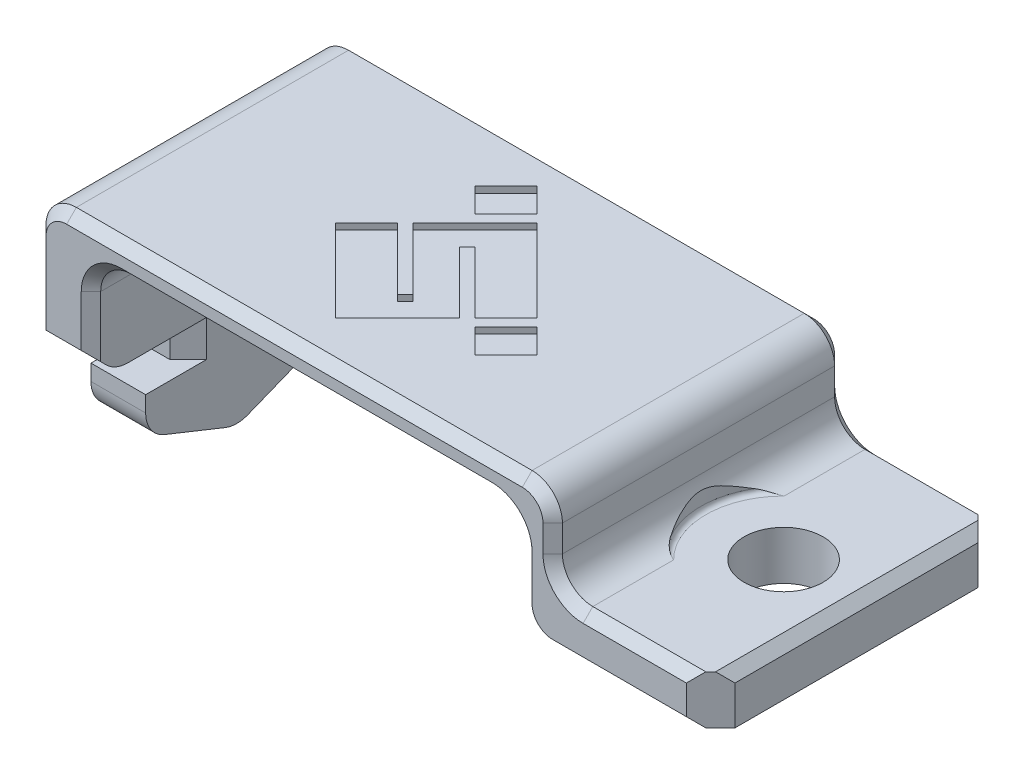
SolidWorks part; units mm, degrees
material "ABS_eSun_GRN"
ref_plane "Front Plane" through (0, 0, 0) normal (0, 0, 1) x (1, 0, 0)
ref_plane "Top Plane" through (0, 0, 0) normal (0, 1, 0) x (1, 0, 0)
ref_plane "Right Plane" through (0, 0, 0) normal (1, 0, 0) x (0, 0, -1)
ref_plane "shelf" through (0, -2.2, 0) normal (0, 1, 0) x (1, 0, 0)
sketch "Sketch1" plane through (0, 0, 0) normal (0, 0, 1) x (1, 0, 0)
  line L0 (-17.75, -9.5) -> (-17.75, 9.5)
  line L1 (-17.75, 9.5) -> (17.75, 9.5)
  line L2 (17.75, 9.5) -> (17.75, 0.8)
  line L5 (20.25, 12) -> (-22.25, 12)
  line L6 (-22.25, 12) -> (-22.25, -9.5)
  line L7 (-22.25, -9.5) -> (-17.75, -9.5)
  line L8 (-22.25, -2.2) -> (31.75, -2.2) construction
  line L9 (-17.75, 7.5) -> (17.75, 7.5) construction
  line L10 (20.25, 4.8) -> (20.25, 12)
  line L13 (20.25, 4.8) -> (33.25, 4.8)
  line L14 (33.25, 0.8) -> (33.25, 4.8)
  line L15 (17.75, 0.8) -> (33.25, 0.8)
  line L16 (-30.0367, 0) -> (47.996, 0) construction
  line L17 (55, -2.2) -> (-55, -2.2) construction
  point P2 (0, 9.5)
  dimension "D1" = 35.5
  dimension "D2" = 2.5
  dimension "D3" = 4.5
  dimension "D4" = 19
  dimension "D8" = 2
  dimension "D9" = 13
  dimension "D10" = 2.5
  dimension "D5" = 3
  dimension "D11" = 4
  dimension "D6" = 11.7
  dimension "D7" = 7.5
extrude "boss_body" add sketch "Sketch1" along normal mid plane 24
fillet "Fillet1" radius 2.5 5 edges at (17.75, 9.5, 0) (-17.75, 9.5, 0) (-22.25, 12, 0) (20.25, 12, 0) (20.25, 4.8, 0)
sketch "Sketch2" plane through (0, 0, 0) normal (1, 0, 0) x (0, 0, -1)
  line L0 (-7.5, -2.2) -> (-7.5, -5.2)
  line L1 (-12, 0.8) -> (-4, 0.8)
  line L2 (-12, 0.8) -> (-12, -9.5)
  line L4 (-4, 0.8) -> (-4, -2.2)
  line L5 (-7.5, -5.2) -> (0, -8.2)
  line L6 (12, 0.8) -> (4, 0.8)
  line L7 (12, 0.8) -> (12, -3.636)
  line L9 (4, 0.8) -> (4, -2.2)
  line L10 (55, -2.2) -> (-55, -2.2) construction
  line L11 (12, -9.5) -> (12, 7) construction
  line L12 (-12, -9.5) -> (-12, 7) construction
  line L13 (0, 12) -> (0, -9.5) construction
  line L14 (0, -8.2) -> (7.5, -5.2)
  line L15 (7.5, -5.2) -> (7.5, -2.2)
  line L16 (-7.5, -5.2) -> (7.5, -5.2) construction
  line L18 (-12, -9.5) -> (12, -9.5)
  line L19 (-12, -9.5) -> (12, -9.5) construction
  line L20 (12, -9.5) -> (12, -3.636)
  line L21 (-4, -2.2) -> (-7.5, -2.2)
  line L22 (7.5, -2.2) -> (4, -2.2)
  point P14 (0, -5.2)
  dimension "D1" = 8
  dimension "D2" = 3
  dimension "D3" = 15
  dimension "D4" = 6
  dimension "D5" = 3
extrude "cut-notch" cut sketch "Sketch2" against normal through all
sketch "Sketch3" plane through (17.75, 0, 0) normal (-1, 0, 0) x (0, 0, 1)
  line L0 (-5, 0.8) -> (-1, -3.2)
  line L2 (-1, -3.2) -> (1, -3.2)
  line L3 (1, -3.2) -> (5, 0.8)
  line L4 (5, 0.8) -> (-5, 0.8)
  line L5 (12, 0.8) -> (-12, 0.8) construction
  point P4 (0, 0.8)
  point P7 (0, -3.2)
  dimension "D1" = 45
  dimension "D2" = 4
  dimension "D3" = 10
extrude "boss_finger" add sketch "Sketch3" against normal blind 2.5
sketch "Sketch4" plane through (0, 0, 0) normal (0, 0, 1) x (1, 0, 0)
  line L0 (-3, 9.5) -> (-1, 7.5)
  line L1 (-17.75, 9.5) -> (17.75, 9.5) construction
  line L2 (-1, 7.5) -> (1, 7.5)
  line L3 (1, 7.5) -> (3, 9.5)
  line L4 (3, 9.5) -> (-3, 9.5)
  line L6 (-15.25, 9.5) -> (15.25, 9.5) construction
  point P4 (0, 7.5)
  point P7 (0, 9.5)
  dimension "D1" = 2
  dimension "D2" = 2
extrude "boss_press" add sketch "Sketch4" along normal mid plane 24 separate body
chamfer "Chamfer3" distance 3 angle 45 2 edges at (0, 7.5, -12) (0, 7.5, 12)
sketch "Sketch6" plane through (0, 0, 0) normal (0, 1, 0) x (1, 0, 0)
  line L0 (20.25, -12) -> (20.25, 12) construction
  circle A0 centre (27.25, 0) radius 3.25
  dimension "D1" = 6.5
  dimension "D2" = 7
extrude "cut_mount_hole" cut sketch "Sketch6" along normal through all and the other way through all
fillet "fillet overhang" radius 2.5 2 edges at (17.75, 0.8, 8.5) (17.75, 0.8, -8.5)
chamfer "Chamfer1" distance 2 angle 45 4 edges at (33.25, 2.8, -12) (33.25, 2.8, 12) (-20, 0.8, -12) (-20, 0.8, 12)
fillet "Fillet2" radius 2.5 5 edges at (-20, 0.8, -10) (-20, 0.8, 10) (-20, -5.2, -7.5) (-20, -5.2, 7.5) (-20, -8.2, 0)
chamfer "chamf_main_faces" distance 0.8 angle 45 29 edges at (25.75, 0.8, -12) (18.4822, 1.5322, -12) (-17.75, 4.9, -12) (17.75, 5.15, -12) (-17.0178, 8.7678, -12) (17.0178, 8.7678, -12) (0, 9.5, -12) (27, 4.8, -12) (20.9822, 5.5322, -12) (20.25, 8.4, -12) (-22.25, 6.15, -12) (19.5178, 11.2678, -12) (-21.5178, 11.2678, -12) (-1, 12, -12) (25.75, 0.8, 12) (18.4822, 1.5322, 12) (-17.75, 4.9, 12) (17.75, 5.15, 12) (-17.0178, 8.7678, 12) (17.0178, 8.7678, 12) (0, 9.5, 12) (27, 4.8, 12) (20.9822, 5.5322, 12) (20.25, 8.4, 12) (-22.25, 6.15, 12) (19.5178, 11.2678, 12) (-21.5178, 11.2678, 12) (-1, 12, 12) (33.25, 4.8, 0)
chamfer "Chamfer4" distance 1.5 angle 45 4 edges at (-22.25, -0.7, -4) (-17.75, -0.7, -4) (-22.25, -0.7, 4) (-17.75, -0.7, 4)
ref_axis "Axis1" through (27.25, 4.8, 0) along (0, -1, 0)
sketch "Sketch7" plane through (0, 0, 0) normal (0, 0, 1) x (1, 0, 0)
  line L0 (27.25, 4.8) -> (20.85, 4.8)
  line L1 (22.75, 4.8) -> (32.05, 4.8) construction
  line L2 (20.45, 5.2) -> (20.45, 8.8)
  line L3 (20.45, 8.8) -> (27.25, 8.8)
  line L4 (27.25, 8.8) -> (27.25, 4.8)
  line L5 (27.25, 4.8) -> (27.25, 0.8) construction
  arc A0 (20.45, 5.2) -> (20.85, 4.8) centre (20.85, 5.2) ccw
  dimension "D2" = 0.4
  dimension "D1" = 6.8
  dimension "D3" = 4
revolve "m6_clearance" cut sketch "Sketch7" angle 360 about axis through (27.25, 4.8, 0) along (0, -1, 0)
sketch "Sketch9" plane through (0, 12, 0) normal (0, 1, 0) x (1, 0, 0)
  line B0 (10.4999, -9.9595) -> (10.4999, 10.0405) construction
  line B1 (-9.5001, -9.9595) -> (10.4999, -9.9595) construction
  line B2 (10.4999, 10.0405) -> (-9.5001, 10.0405)
  line B3 (-9.5001, 10.0405) -> (-9.5001, -9.9595) construction
  line B4 (-4.8561, 6.7053) -> (-2.3105, 9.2509)
  line B5 (-2.8762, 4.7254) -> (-4.8561, 6.7053)
  line B6 (-0.3306, 7.271) -> (-2.8762, 4.7254)
  line B7 (-2.3105, 9.2509) -> (-0.3306, 7.271)
  line B8 (-0.5427, 2.392) -> (-1.1791, 1.7556)
  line B9 (4.5485, -2.6992) -> (-0.5427, 2.392)
  line B10 (7.094, -0.1536) -> (4.5485, -2.6992)
  line B11 (0.3058, 6.6346) -> (7.094, -0.1536)
  line B12 (-4.7853, 1.5434) -> (0.3058, 6.6346)
  line B13 (0.3058, -3.5477) -> (-4.7853, 1.5434)
  line B14 (-0.3306, -4.1841) -> (0.3058, -3.5477)
  line B15 (-7.9673, -1.6385) -> (-5.4217, 0.907)
  line B16 (-1.1791, -8.4268) -> (-7.9673, -1.6385)
  line B17 (3.9121, -3.3356) -> (-1.1791, -8.4268)
  line B18 (-1.1791, 1.7556) -> (3.9121, -3.3356)
  line B19 (7.7304, -0.79) -> (9.7103, -2.7699)
  line B20 (5.1849, -3.3356) -> (7.7304, -0.79)
  line B21 (7.1648, -5.3155) -> (5.1849, -3.3356)
  line B22 (9.7103, -2.7699) -> (7.1648, -5.3155)
  line B23 (-5.4217, 0.907) -> (-0.3306, -4.1841)
sketch_block_instance "scuttle logo plain-1"
sketch_block "Block1"
other "DetailItem3"
other "DetailItem4"
extrude "cut_LOGO" cut sketch "Sketch9" against normal blind 0.5 contours B23 B15 B16 B17 B18 B8 B9 B10 B11 B12 B13 B14 | B7 B4 B5 B6 | B22 B19 B20 B21 region at (-2.5933, 12, -6.9882) region at (-0.4366, 12, 0.8961) region at (7.4476, 12, 3.0528)
sketch "Sketch10" plane through (0, 9.5, 0) normal (0, -1, 0) x (1, 0, 0)
  line L0 (-15.25, -6.8478) -> (-4.3688, -6.8478) construction
  line L1 (-15.25, 11.2) -> (-15.25, -11.2) construction
  text T0 "v1.1\r\n"
extrude "cut_version" cut sketch "Sketch10" against normal blind 0.5
equation "\"H\"=21.1995"
equation "\"d\"=10"
equation "\"t\"=8.4"
equation "\"D10@Sketch1\"=\"D2@Sketch1\""
equation "\"t1\"=2.5"
equation "\"D1@boss_finger\" = \"t1\""
